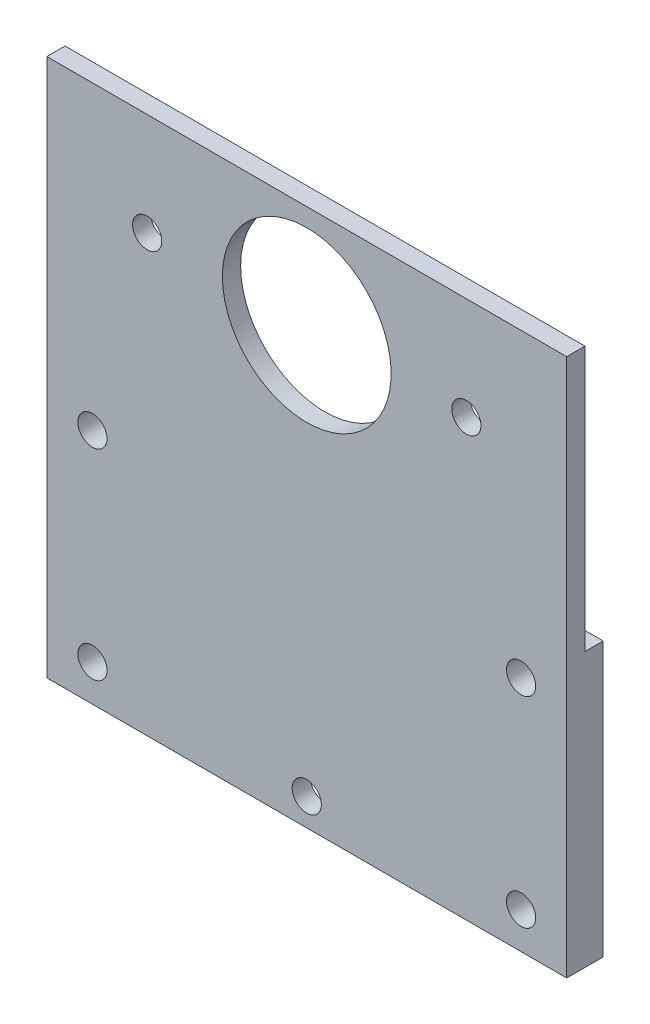
SolidWorks part; units mm, degrees
ref_plane "Ebene vorne" through (0, 0, 0) normal (0, 0, 1) x (1, 0, 0)
ref_plane "Ebene oben" through (0, 0, 0) normal (0, 1, 0) x (1, 0, 0)
ref_plane "Ebene rechts" through (0, 0, 0) normal (1, 0, 0) x (0, 0, -1)
sketch "Skizze1" plane through (0, 0, 0) normal (0, 0, 1) x (1, 0, 0)
  line L0 (0, 0) -> (0, 72.9146) construction
  line L1 (-28.5, 59) -> (28.5, 59)
  line L2 (28.5, 59) -> (28.5, 0)
  line L3 (28.5, 0) -> (-28.5, 0)
  line L4 (-28.5, 59) -> (-28.5, 0)
  point P7 (0, 59)
  dimension "D1" = 57
  dimension "D2" = 59
extrude "Grundkörper" add sketch "Skizze1" along normal blind 2
sketch "Skizze2" plane through (0, 0, 0) normal (0, 0, -1) x (-1, 0, 0)
  line L0 (0, 0) -> (0, 59.4137) construction
  line L1 (-18.082, 47.75) -> (18.082, 47.75) construction
  line L2 (-28.5, 59) -> (28.5, 59) construction
  circle A0 centre (0, 47.75) radius 9.25
  circle A1 centre (-17.5, 47.75) radius 1.6
  circle A2 centre (17.5, 47.75) radius 1.6
  dimension "D1" = 3.2
  dimension "D2" = 18.5
  dimension "D3" = 11.25
  dimension "D4" = 35
extrude "Bohrungen_Kugelroller" cut sketch "Skizze2" against normal through all
sketch "Skizze3" plane through (0, 0, 0) normal (0, 0, -1) x (-1, 0, 0)
  line L0 (0, 59) -> (0, -0.4438) construction
  line L1 (-28.5, 59) -> (28.5, 59) construction
  line L2 (-28.5, 30) -> (-18.5, 30)
  line L3 (-28.5, 0) -> (-28.5, 59) construction
  line L4 (-18.5, 30) -> (-18.5, 0)
  line L5 (28.5, 0) -> (18.5, 0)
  line L6 (28.5, 30) -> (28.5, 0)
  line L7 (-28.5, 30) -> (-28.5, 0)
  line L8 (-28.5, 0) -> (-18.5, 0)
  line L9 (28.5, 0) -> (-28.5, 0) construction
  line L10 (18.5, 30) -> (18.5, 0)
  line L11 (28.5, 30) -> (18.5, 30)
  dimension "D1" = 10
  dimension "D2" = 30
extrude "Aufsatz_Getriebehalter" add sketch "Skizze3" along normal blind 2
sketch "Skizze4" plane through (0, 0, -2) normal (0, 0, -1) x (-1, 0, 0)
  line L0 (0, 57.8388) -> (0, -14.2703) construction
  line L1 (24, 15) -> (-24, 15) construction
  line L2 (-23.5, 30) -> (-23.5, -0.0042) construction
  line L3 (24, 22.0317) -> (24, 7.9683) construction
  line L4 (-18.5, 15) -> (-29.1223, 15) construction
  line L5 (-18.5, 0) -> (-18.5, 30) construction
  line L7 (-18.5, 30) -> (-28.5, 30) construction
  circle A0 centre (-23.5, 26) radius 1.6
  circle A1 centre (23.5, 26) radius 1.6
  circle A2 centre (23.5, 4) radius 1.6
  circle A3 centre (-23.5, 4) radius 1.6
  point P10 (0, 15)
  dimension "D1" = 3.2
  dimension "D2" = 22
extrude "Bohrungen_Getriebehalter" cut sketch "Skizze4" against normal through all
sketch "Skizze5" plane through (0, 0, 0) normal (0, 0, -1) x (-1, 0, 0)
  line L0 (0, 61.2734) -> (0, -5.0948) construction
  line L1 (18.5, 0) -> (-18.5, 0) construction
  circle A0 centre (0, 3) radius 1.6
  dimension "D1" = 3.2
  dimension "D2" = 3
extrude "Bohrung_Halterung" cut sketch "Skizze5" against normal through all
sketch "Skizze8" plane through (0, 0, 0) normal (0, 0, -1) x (-1, 0, 0)
  line L0 (-16.5, 13) -> (-16.5, 3)
  line L1 (-16.5, 3) -> (-4, 3)
  line L2 (-4, 3) -> (-4, 7.5)
  line L3 (-4, 7.5) -> (-16.5, 13)
  line L4 (-4, 9.5) -> (-4, 20.5)
  line L5 (-4, 20.5) -> (-16.5, 15)
  line L6 (-16.5, 15) -> (-4, 9.5)
  line L7 (-16.5, 28) -> (-16.5, 17)
  line L8 (-16.5, 17) -> (-4, 22.5)
  line L9 (-4, 22.5) -> (-16.5, 28)
  line L10 (-16.5, 30) -> (-4, 24.5)
  line L11 (-4, 24.5) -> (-4, 35.5)
  line L12 (-4, 35.5) -> (-16.5, 30)
  line L13 (0, 0) -> (0, 65.3922) construction
  line L14 (-26.178, 32) -> (-16.5, 32)
  line L15 (-16.5, 32) -> (-4, 37.5)
  line L16 (-18.5, 0) -> (-18.5, 30) construction
  line L17 (18.5, 0) -> (-18.5, 0) construction
  line L18 (-4, 37.5) -> (-26.178, 37.5)
  line L19 (-26.178, 37.5) -> (-26.178, 32)
  line L20 (-18.5, 30) -> (-28.5, 30) construction
  line L21 (26.178, 37.5) -> (26.178, 32)
  line L22 (4, 37.5) -> (26.178, 37.5)
  line L23 (16.5, 32) -> (4, 37.5)
  line L24 (26.178, 32) -> (16.5, 32)
  line L25 (4, 35.5) -> (16.5, 30)
  line L26 (4, 24.5) -> (4, 35.5)
  line L27 (16.5, 30) -> (4, 24.5)
  line L28 (4, 22.5) -> (16.5, 28)
  line L29 (16.5, 17) -> (4, 22.5)
  line L30 (16.5, 28) -> (16.5, 17)
  line L31 (16.5, 15) -> (4, 9.5)
  line L32 (4, 20.5) -> (16.5, 15)
  line L33 (4, 9.5) -> (4, 20.5)
  line L34 (4, 7.5) -> (16.5, 13)
  line L35 (4, 3) -> (4, 7.5)
  line L36 (16.5, 3) -> (4, 3)
  line L37 (16.5, 13) -> (16.5, 3)
  point P22 (0, 0)
  point P23 (0, 0)
  dimension "D1" = 2
  dimension "D2" = 4
  dimension "D3" = 3
  dimension "D4" = 10
  dimension "D5" = 2
  dimension "D6" = 2
  dimension "D7" = 2
  dimension "D8" = 11
  dimension "D9" = 2
extrude "Schnitt-Linear austragen4" cut sketch "Skizze8" against normal blind 1
fillet "Verrundung_Ausschnitte" radius 1 34 edges at (-26.178, 34.75, 1) (-21.339, 32, 1) (-10.25, 34.75, 1) (-15.089, 37.5, 1) (-10.25, 32.75, 1) (-10.25, 27.25, 1) (-4, 30, 1) (-10.25, 25.25, 1) (-16.5, 22.5, 1) (-10.25, 19.75, 1) (-10.25, 12.25, 1) (-4, 15, 1) (-10.25, 17.75, 1) (-10.25, 10.25, 1) (-16.5, 8, 1) (-10.25, 3, 1) (-4, 5.25, 1) (4, 5.25, 1) (10.25, 3, 1) (16.5, 8, 1) (10.25, 10.25, 1) (10.25, 17.75, 1) (4, 15, 1) (10.25, 12.25, 1) (10.25, 19.75, 1) (16.5, 22.5, 1) (10.25, 25.25, 1) (4, 30, 1) (10.25, 27.25, 1) (10.25, 32.75, 1) (10.25, 34.75, 1) (21.339, 32, 1) (26.178, 34.75, 1) (15.089, 37.5, 1)
fillet "Verrundung4" radius 1 34 edges at (5.3929, 37.2071, 0.7071) (4.2929, 3.2929, 0.7071) (16.2071, 3.2929, 0.7071) (4.2929, 9.9489, 0.7071) (15.7727, 15, 0.7071) (4.2929, 7.3089, 0.7071) (16.2071, 12.5511, 0.7071) (4.2929, 20.0511, 0.7071) (4.7273, 22.5, 0.7071) (16.2071, 17.4489, 0.7071) (16.2071, 27.5511, 0.7071) (4.2929, 35.0511, 0.7071) (4.2929, 24.9489, 0.7071) (15.7727, 30, 0.7071) (16.5616, 32.2929, 0.7071) (25.8851, 32.2929, 0.7071) (25.8851, 37.2071, 0.7071) (-16.2071, 3.2929, 0.7071) (-16.2071, 12.5511, 0.7071) (-4.2929, 3.2929, 0.7071) (-4.2929, 7.3089, 0.7071) (-4.2929, 20.0511, 0.7071) (-4.2929, 9.9489, 0.7071) (-15.7727, 15, 0.7071) (-16.2071, 17.4489, 0.7071) (-16.2071, 27.5511, 0.7071) (-4.7273, 22.5, 0.7071) (-15.7727, 30, 0.7071) (-4.2929, 35.0511, 0.7071) (-4.2929, 24.9489, 0.7071) (-5.3929, 37.2071, 0.7071) (-16.5616, 32.2929, 0.7071) (-25.8851, 37.2071, 0.7071) (-25.8851, 32.2929, 0.7071)
